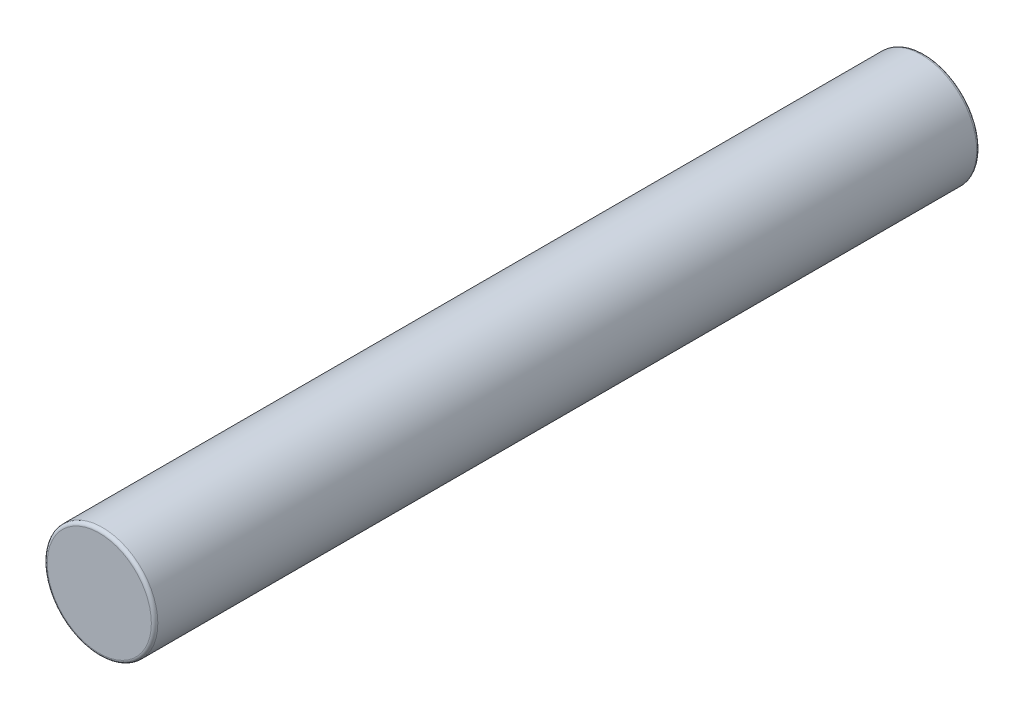
SolidWorks part; units mm, degrees
ref_plane "Front Plane" through (0, 0, 0) normal (0, 0, 1) x (1, 0, 0)
ref_plane "Top Plane" through (0, 0, 0) normal (0, 1, 0) x (1, 0, 0)
ref_plane "Right Plane" through (0, 0, 0) normal (1, 0, 0) x (0, 0, -1)
sketch "Sketch1" plane through (0, 0, 0) normal (0, 0, 1) x (1, 0, 0)
  circle A0 centre (0, 0) radius 8.509
  dimension "D1" = 17.018
extrude "Boss-Extrude1" add sketch "Sketch1" along normal blind 127
fillet "Fillet1" radius 0.5 2 edges at (8.509, 0, 0) (8.509, 0, 127)
ref_axis "Axis1" through (0, 0, 126.5) along (0, 0, -1)
